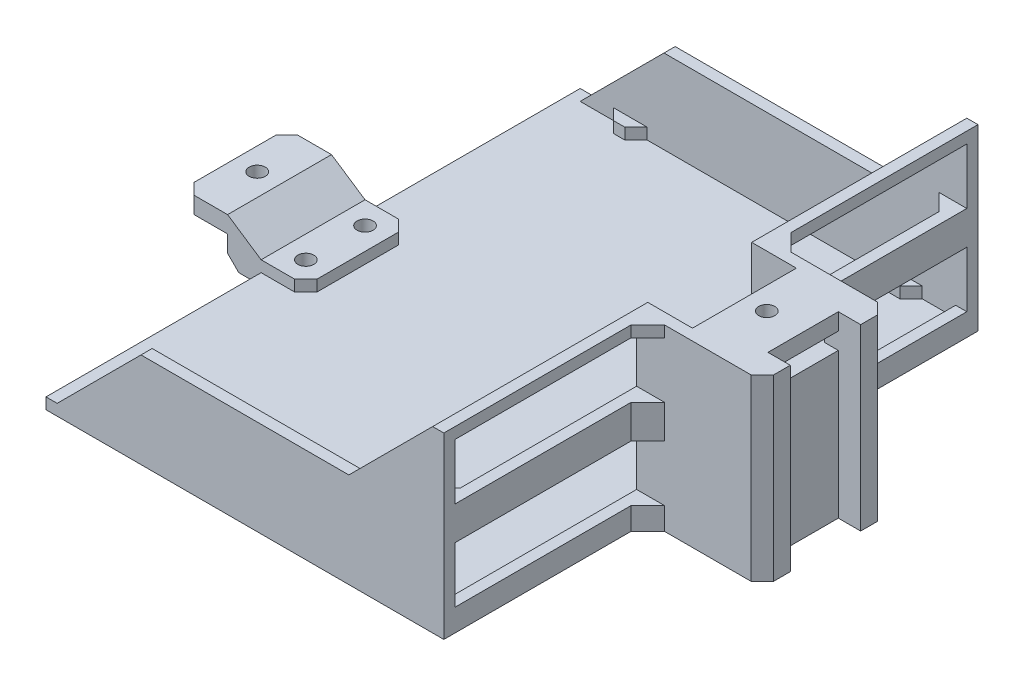
SolidWorks part; units mm, degrees
ref_plane "Front Plane" through (0, 0, 0) normal (0, 0, 1) x (1, 0, 0)
ref_plane "Top Plane" through (0, 0, 0) normal (0, 1, 0) x (1, 0, 0)
ref_plane "Right Plane" through (0, 0, 0) normal (1, 0, 0) x (0, 0, -1)
sketch "Sketch1" plane through (0, 0, 0) normal (0, 1, 0) x (1, 0, 0)
  circle A0 centre (0, 0) radius 75.692 construction
  dimension "D1" = 151.384
sketch "Sketch3" plane through (0, 0, 0) normal (0, 1, 0) x (1, 0, 0)
  line L1 (-45.2113, -60.706) -> (45.2113, -60.706)
  line L2 (-45.2113, -60.706) -> (-45.2113, 60.706)
  line L3 (-45.2113, 60.706) -> (45.2113, 60.706)
  line L4 (45.2113, -60.706) -> (45.2113, 60.706)
  line L5 (-45.2113, -60.706) -> (45.2113, 60.706) construction
  line L6 (-45.2113, 60.706) -> (45.2113, -60.706) construction
  circle A0 centre (0, 0) radius 75.692 construction
  point P0 (0, 0)
  dimension "D1" = 121.412
extrude "Boss-Extrude4" add sketch "Sketch3" along normal blind 2.54
sketch "Sketch6" plane through (0, 2.54, 0) normal (0, 1, 0) x (1, 0, 0)
  line L0 (-1000, 0) -> (49000, 0) construction
  line L1 (45.2113, -60.706) -> (45.2113, 60.706) construction
  line L2 (45.2113, 60.706) -> (-45.2113, 60.706) construction
  line L3 (45.2113, -60.706) -> (45.2113, 60.706)
  line L4 (45.2113, 60.706) -> (-45.2113, 60.706)
  line L5 (-45.2113, 60.706) -> (-45.2113, 58.166)
  line L6 (-45.2113, 60.706) -> (-45.2113, -60.706) construction
  line L7 (-45.2113, 58.166) -> (42.6713, 58.166)
  line L8 (42.6713, 58.166) -> (42.6713, -58.166)
  line L10 (-45.2113, -58.166) -> (42.6713, -58.166)
  line L11 (-45.2113, -60.706) -> (-45.2113, -58.166)
  line L12 (45.2113, -60.706) -> (-45.2113, -60.706)
  dimension "D1" = 2.54
extrude "Boss-Extrude5" add sketch "Sketch6" along normal blind 38.1
sketch "Sketch7" plane through (0, 0, 60.706) normal (0, 0, 1) x (1, 0, 0)
  line L0 (42.6713, 2.54) -> (-45.2113, 2.54) construction
  line L1 (42.6713, 40.64) -> (42.6713, 2.54) construction
  line L2 (42.6713, 2.54) -> (-45.2113, 2.54) construction
  line L3 (42.6713, 40.64) -> (42.6713, 2.54) construction
  line L4 (0, -1000) -> (0, 49000) construction
  line L5 (-957.3287, 21.59) -> (49042.6713, 21.59) construction
  line L6 (-42.6713, 40.64) -> (-42.6713, 2.54) construction
  line L7 (-42.6713, 2.54) -> (-23.6213, 21.59)
  line L8 (-23.6213, 21.59) -> (23.6213, 21.59)
  line L9 (23.6213, 21.59) -> (42.6713, 40.64)
  line L10 (42.6713, 40.64) -> (-45.2113, 40.64)
  line L11 (-45.2113, 40.64) -> (-45.2113, 2.54)
  line L12 (-45.2113, 2.54) -> (-42.6713, 2.54)
  point P9 (42.6713, 21.59)
  dimension "D1" = 45
  dimension "D2" = 45
extrude "Cut-Extrude2" cut sketch "Sketch7" against normal through all
sketch "Sketch8" plane through (0, 0, 0) normal (0, 1, 0) x (1, 0, 0)
  line L0 (-1000, 0) -> (49000, 0) construction
  line L1 (45.2113, 14.351) -> (68.707, 14.351)
  line L2 (45.2113, -60.706) -> (45.2113, 60.706) construction
  line L3 (68.707, 14.351) -> (71.247, 11.811)
  line L4 (71.247, 11.811) -> (71.247, 8.001)
  line L5 (71.247, 8.001) -> (66.167, 8.001)
  line L6 (66.167, 8.001) -> (66.167, -8.001)
  line L7 (45.2113, 14.351) -> (45.2113, -14.351)
  line L8 (45.2113, -14.351) -> (68.707, -14.351)
  line L9 (68.707, -14.351) -> (71.247, -11.811)
  line L10 (71.247, -11.811) -> (71.247, -8.001)
  line L11 (71.247, -8.001) -> (66.167, -8.001)
  point P13 (45.2113, 0)
  point P17 (66.167, 0)
  dimension "D1" = 16.002
  dimension "D2" = 5.08
  dimension "D3" = 6.35
  dimension "D4" = 3.81
  dimension "D5" = 45
  dimension "D6" = 66.167
extrude "Boss-Extrude6" add sketch "Sketch8" along normal up to surface (40.64 mm away) up to face at (43.518, 40.64, 0)
sketch "Sketch9" plane through (0, 40.64, 0) normal (0, 1, 0) x (1, 0, 0)
  line L0 (-1000, 0) -> (49000, 0) construction
  line L1 (52.8313, -11.811) -> (52.8313, 11.811)
  line L2 (52.8313, 11.811) -> (42.6713, 11.811)
  line L3 (42.6713, 58.166) -> (42.6713, -58.166) construction
  line L4 (42.6713, 11.811) -> (42.6713, -11.811)
  line L5 (52.8313, -11.811) -> (42.6713, -11.811)
  line L6 (68.707, 14.351) -> (45.2113, 14.351) construction
  point P10 (42.6713, 0)
  point P11 (52.8313, 0)
  dimension "D1" = 10.16
  dimension "D2" = 2.54
extrude "Cut-Extrude3" cut sketch "Sketch9" against normal offset from surface (35.56 mm away) 2.54 up to face at (-21.9706, 2.54, 0)
sketch "Sketch11" plane through (0, 2.54, 0) normal (0, 1, 0) x (1, 0, 0)
  line L5 (35.0513, 58.166) -> (27.4313, 58.166)
  line L6 (-42.6713, 58.166) -> (42.6713, 58.166) construction
  line L7 (27.4313, 58.166) -> (29.9713, 55.626)
  line L8 (29.9713, 55.626) -> (32.5113, 55.626)
  line L9 (32.5113, 55.626) -> (35.0513, 58.166)
  line L10 (42.6713, 58.166) -> (42.6713, -58.166) construction
  line L11 (-1000, 0) -> (49000, 0) construction
  line L12 (0, -1000) -> (0, 49000) construction
  line L13 (-29.9713, 55.626) -> (-32.5113, 55.626)
  line L14 (-27.4313, 58.166) -> (-29.9713, 55.626)
  line L15 (-35.0513, 58.166) -> (-27.4313, 58.166)
  line L16 (-32.5113, 55.626) -> (-35.0513, 58.166)
  line L17 (29.9713, -55.626) -> (32.5113, -55.626)
  line L18 (27.4313, -58.166) -> (29.9713, -55.626)
  line L19 (35.0513, -58.166) -> (27.4313, -58.166)
  line L20 (32.5113, -55.626) -> (35.0513, -58.166)
  line L21 (-27.4313, -58.166) -> (-29.9713, -55.626)
  line L22 (-35.0513, -58.166) -> (-27.4313, -58.166)
  line L23 (-32.5113, -55.626) -> (-35.0513, -58.166)
  line L24 (-29.9713, -55.626) -> (-32.5113, -55.626)
  dimension "D1" = 45
  dimension "D2" = 45
  dimension "D3" = 2.54
  dimension "D4" = 2.54
  dimension "D5" = 7.62
extrude "Boss-Extrude7" add sketch "Sketch11" along normal up to surface (2.54 mm away) up to face at (47.7513, 5.08, 0)
sketch "Sketch12" plane through (52.8313, 0, 0) normal (-1, 0, 0) x (0, 0, 1)
  line L0 (11.811, 5.08) -> (11.811, 40.64) construction
  line L1 (11.811, 36.83) -> (-11.811, 36.83)
  line L2 (11.811, 36.83) -> (11.811, 33.02)
  line L3 (11.811, 33.02) -> (-11.811, 33.02)
  line L4 (-11.811, 36.83) -> (-11.811, 33.02)
  line L5 (-11.811, 5.08) -> (-11.811, 40.64) construction
  line L6 (11.811, 40.64) -> (-11.811, 40.64) construction
  dimension "D1" = 3.81
  dimension "D2" = 3.81
extrude "Cut-Extrude4" cut sketch "Sketch12" against normal blind 10.16
sketch "Sketch13" plane through (62.9913, 0, 0) normal (-1, 0, 0) x (0, 0, 1)
  line L0 (11.811, 36.83) -> (-11.811, 36.83) construction
  line L1 (-8.001, 36.83) -> (8.001, 36.83)
  line L2 (-8.001, 36.83) -> (-8.001, 33.02)
  line L3 (-8.001, 33.02) -> (8.001, 33.02)
  line L4 (8.001, 36.83) -> (8.001, 33.02)
  line L5 (-8.001, 40.64) -> (-8.001, 0) construction
  line L6 (-11.811, 33.02) -> (11.811, 33.02) construction
  line L7 (8.001, 40.64) -> (8.001, 0) construction
  point P12 (0, 0)
extrude "Cut-Extrude5" cut sketch "Sketch13" against normal through all
sketch "Sketch15" plane through (0, 0, 0) normal (0, 0, 1) x (1, 0, 0)
  line L0 (0, -1000) -> (0, 49000) construction
  line L2 (62.9913, 36.83) -> (62.9913, 33.02) construction
  line L3 (62.9913, 33.02) -> (52.8313, 33.02) construction
  line L4 (62.9913, 36.83) -> (52.8313, 36.83) construction
  line L5 (62.9913, 33.02) -> (52.8313, 33.02) construction
  line L6 (62.9913, 36.83) -> (62.9913, 33.02) construction
  line L7 (62.9913, 36.83) -> (52.8313, 36.83) construction
  line L8 (-62.9913, 36.83) -> (-52.8313, 36.83) construction
  line L9 (-62.9913, 36.83) -> (-62.9913, 33.02) construction
  line L10 (-62.9913, 33.02) -> (-52.8313, 33.02) construction
  line L11 (-998.1426, 21.59) -> (49001.8574, 21.59) construction
  line L13 (-62.9913, 10.16) -> (-52.8313, 10.16)
  line L14 (-62.9913, 6.35) -> (-62.9913, 10.16)
  line L15 (-62.9913, 6.35) -> (-52.8313, 6.35)
  line L16 (-23.6213, 21.59) -> (23.6213, 21.59) construction
  line L17 (-52.8313, 6.35) -> (-52.8313, 0)
  line L18 (-52.8313, 0) -> (-45.2113, 0)
  line L19 (-45.2113, 0) -> (-45.2113, 2.54)
  line L20 (-45.2113, 2.54) -> (-35.0513, 2.54)
  line L21 (-35.0513, 2.54) -> (-42.6713, 2.54) construction
  line L23 (-35.0513, 2.54) -> (-35.0513, 5.08)
  line L24 (-35.0513, 5.08) -> (-45.2113, 5.08)
  line L25 (-45.2113, 5.08) -> (-52.8313, 10.16)
  line L26 (-27.4313, 5.08) -> (-35.0513, 5.08) construction
  line L27 (52.8313, 5.08) -> (42.6713, 5.08) construction
  line L28 (52.8313, 5.08) -> (42.6713, 5.08) construction
  point P31 (-49.0213, 33.9341)
  point P32 (0, 0)
extrude "Boss-Extrude9" add sketch "Sketch15" against normal up to surface and the other way up to surface up to face at (52.8313, 28.8925, -11.811) other way up to face at (52.8313, 28.8925, 11.811)
hole_wizard "CBORE for #6 Pan Head Machine Screw1" positions "Sketch16" profile "Sketch17" counterbore size "#6" standard "ANSI Inch" end condition through all
sketch "Sketch16" plane through (0, 0, 0) normal (0, -1, 0) x (-1, 0, 0)
  line L0 (-47.7513, -988.189) -> (-47.7513, 49011.811) construction
  line L1 (-52.8313, 11.811) -> (-42.6713, 11.811) construction
  line L2 (-1000, 0) -> (49000, 0) construction
  line L3 (40.1313, -988.189) -> (40.1313, 49011.811) construction
  line L4 (45.2113, 11.811) -> (35.0513, 11.811) construction
  line L5 (-1047.7513, 6.731) -> (48952.2487, 6.731) construction
  line L6 (-1047.7513, -6.731) -> (48952.2487, -6.731) construction
  line L7 (-52.8313, 11.811) -> (-42.6713, 1.651) construction
  line L8 (-42.6713, 11.811) -> (-42.6713, -11.811) construction
  point P0 (-47.7513, 6.731)
  point P7 (-47.7513, 11.811)
  point P18 (-47.7513, -6.731)
  point P24 (40.1313, 11.811)
  point P34 (40.1313, 6.731)
  point P36 (40.1313, -6.7235)
  point P47 (0, 0)
  dimension "D1" = 45
sketch "Sketch17" plane through (47.7513, 0, -6.731) normal (1, 0, 0) x (0, 0, -1)
  line L0 (0, 0) -> (0, 40.64)
  line L1 (0, 40.64) -> (1.8288, 40.64)
  line L3 (1.8288, 40.64) -> (1.8288, 2.4638)
  line L4 (1.8288, 2.4638) -> (3.7706, 2.4638)
  line L5 (3.7706, 2.4638) -> (3.7706, 0)
  line L7 (3.7706, 0) -> (0, 0)
  line L11 (0, -6.35) -> (0, 107.95) construction
  dimension "Thru Hole Dia." = 3.6576
  dimension "Thru Hole Depth" = 40.64
  dimension "C'Bore Dia." = 7.5413
  dimension "C'Bore Depth" = 2.4638
hole_wizard "#6 Clearance Hole1" positions "Sketch19" profile "Sketch20" hole size "#6" standard "ANSI Inch" end condition through all
sketch "Sketch19" plane through (0, 40.64, 0) normal (0, 1, 0) x (1, 0, 0)
  line L0 (-1000, 0) -> (49000, 0) construction
  line L1 (0, -1000) -> (0, 49000) construction
  line L2 (57.9113, -988.189) -> (57.9113, 49011.811) construction
  line L3 (62.9913, 11.811) -> (52.8313, 11.811) construction
  point P6 (57.9113, 0)
  point P13 (-57.9113, 0)
  point P20 (57.9113, 11.811)
  point P22 (0, 0)
sketch "Sketch20" plane through (-57.9113, 40.64, 0) normal (1, 0, 0) x (0, 0, 1)
  line L0 (0, 0) -> (0, 40.64)
  line L1 (0, 40.64) -> (1.8288, 40.64)
  line L2 (1.8288, 40.64) -> (1.8288, 0)
  line L5 (1.8288, 0) -> (0, 0)
  line L11 (0, -6.35) -> (0, 107.95) construction
  dimension "Thru Hole Dia." = 3.6576
  dimension "Thru Hole Depth" = 40.64
sketch "Sketch21" plane through (42.6713, 0, 0) normal (-1, 0, 0) x (0, 0, 1)
  line L0 (-1058.166, 21.59) -> (48941.834, 21.59) construction
  line L1 (-58.166, 40.64) -> (-58.166, 2.54) construction
  line L2 (0, -1000) -> (0, 49000) construction
  line L3 (-11.811, 0) -> (11.811, 0) construction
  line L5 (-58.166, 5.08) -> (-14.351, 5.08)
  line L6 (-58.166, 5.08) -> (-58.166, 17.78)
  line L7 (-58.166, 17.78) -> (-14.351, 17.78)
  line L8 (-14.351, 5.08) -> (-14.351, 17.78)
  line L9 (-1008.4655, 5.08) -> (48991.5345, 5.08) construction
  line L11 (-11.811, 5.08) -> (11.811, 5.08) construction
  line L12 (-14.351, 40.64) -> (-14.351, 0) construction
  line L13 (-58.166, 40.64) -> (-58.166, 21.59) construction
  line L14 (-58.166, 25.4) -> (-14.351, 25.4)
  line L15 (-14.351, 38.1) -> (-14.351, 25.4)
  line L16 (-58.166, 38.1) -> (-14.351, 38.1)
  line L17 (-58.166, 38.1) -> (-58.166, 25.4)
  line L18 (58.166, 17.78) -> (14.351, 17.78)
  line L19 (14.351, 5.08) -> (14.351, 17.78)
  line L20 (58.166, 5.08) -> (14.351, 5.08)
  line L21 (58.166, 5.08) -> (58.166, 17.78)
  line L22 (58.166, 38.1) -> (58.166, 25.4)
  line L23 (58.166, 38.1) -> (14.351, 38.1)
  line L24 (14.351, 38.1) -> (14.351, 25.4)
  line L25 (58.166, 25.4) -> (14.351, 25.4)
  point P5 (-58.166, 21.59)
  point P10 (0, 0)
  dimension "D1" = 12.7
extrude "Cut-Extrude6" cut sketch "Sketch21" against normal through all
chamfer "Chamfer1" distance 2.54 angle 45 5 edges at (-62.9913, 8.255, -11.811) (-62.9913, 8.255, 11.811) (-35.0513, 3.81, 11.811) (-35.0513, 3.81, -11.811) (-52.8313, 0, 0)
chamfer "Chamfer2" distance 3.81 angle 45 8 edges at (45.2113, 2.54, 14.351) (45.2113, 21.59, 14.351) (45.2113, 39.37, 14.351) (45.2113, 2.54, -14.351) (45.2113, 21.59, -14.351) (45.2113, 39.37, -14.351) (42.6713, 21.59, -58.166) (42.6713, 21.59, 58.166)
